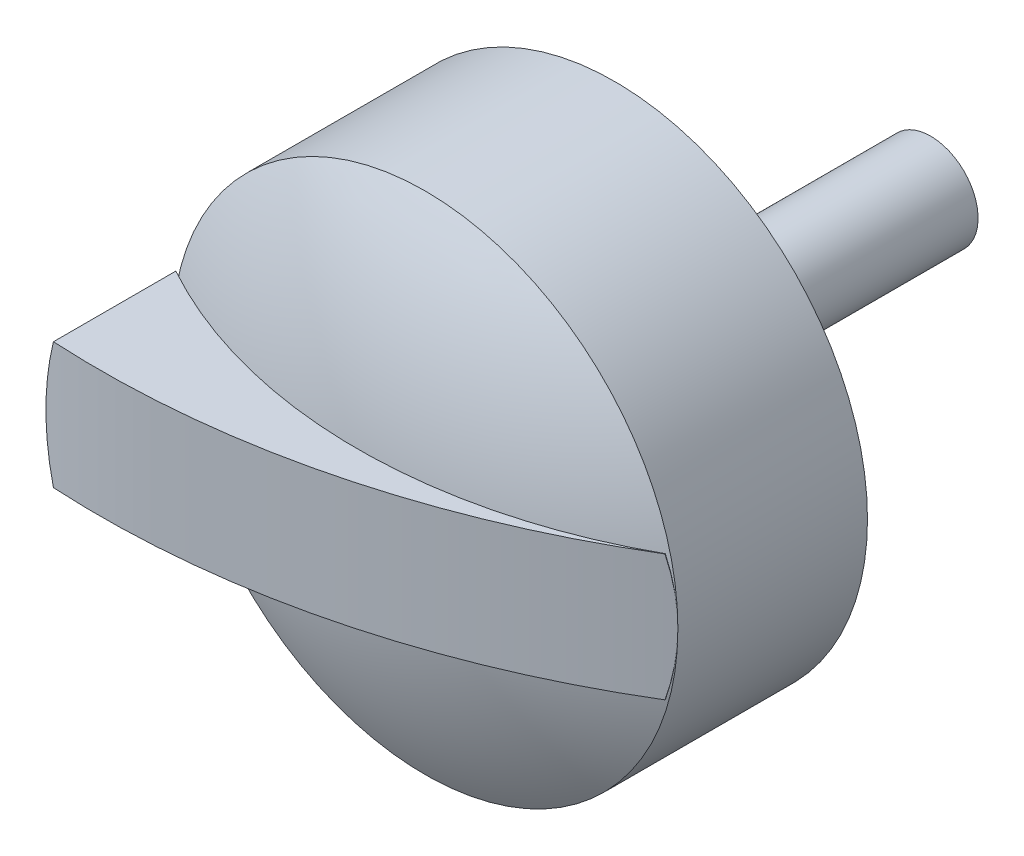
SolidWorks part; units mm, degrees
ref_plane "Front Plane" through (0, 0, 0) normal (0, 0, 1) x (1, 0, 0)
ref_plane "Top Plane" through (0, 0, 0) normal (0, 1, 0) x (1, 0, 0)
ref_plane "Right Plane" through (0, 0, 0) normal (1, 0, 0) x (0, 0, -1)
sketch "Sketch1" plane through (0, 0, 0) normal (0, 0, 1) x (1, 0, 0)
  circle A0 centre (0, 0) radius 4.5
  circle A1 centre (0, 0) radius 7.5
  circle A2 centre (0, 0) radius 8
  dimension "D1" = 9
  dimension "D2" = 15
  dimension "D3" = 16
extrude "Boss-Extrude1" add sketch "Sketch1" along normal blind 6 contours A0 | A2 A1 region at (0, 0, 0) region at (-7.7737, 0, 0)
sketch "Sketch4" plane through (0, 0, 0) normal (1, 0, 0) x (0, 0, -1)
  line L0 (-228.4772, 0) -> (376.2589, 0) construction
  line L1 (-8.1436, 0) -> (-6, 0)
  line L2 (-6, 0) -> (-6, -8)
  arc A0 (-6, -8) -> (-8.1436, 0) centre (7.8564, 0) cw
  dimension "D1" = 16
revolve "Revolve1" add sketch "Sketch4" angle 360 about L0
sketch "Sketch8" plane through (0, 0, 0) normal (0, 0, -1) x (-1, 0, 0)
  circle A0 centre (0, 0) radius 1.5
  dimension "D1" = 3
extrude "Boss-Extrude3" add sketch "Sketch8" along normal blind 10
sketch "Sketch9" plane through (0, 0, 0) normal (0, 1, 0) x (1, 0, 0)
  line L0 (-8, -6) -> (-8, -10)
  arc A0 (-8, -10) -> (8, -6) centre (-6.2356, 16.9423) ccw
  arc A1 (-8, -6) -> (8, -6) centre (0, 7.8564) ccw
  dimension "D2" = 27
  dimension "D3" = 16
  dimension "D1" = 4
extrude "Boss-Extrude4" add sketch "Sketch9" along normal blind 2 and the other way blind 2 separate body
ref_plane "Plane1" through (0, 0, 10) normal (0, 0, 1) x (1, 0, 0)
sketch "Sketch10" plane through (0, 0, 10) normal (0, 0, 1) x (1, 0, 0)
  circle A0 centre (0, 0) radius 8.2733
  circle A1 centre (0, 0) radius 8
  dimension "D1" = 16
  dimension "D2" = 16.5466
extrude "Cut-Extrude1" cut sketch "Sketch10" against normal blind 15 and the other way blind 2
